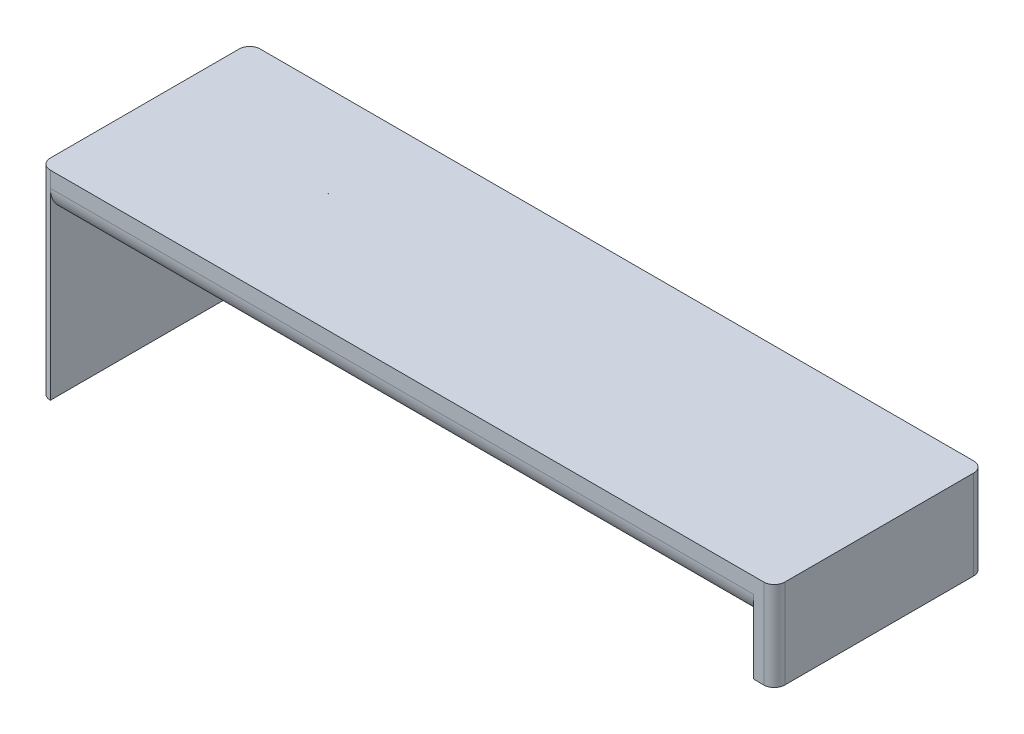
SolidWorks part; units mm, degrees
ref_plane "Front Plane" through (0, 0, 0) normal (0, 0, 1) x (1, 0, 0)
ref_plane "Top Plane" through (0, 0, 0) normal (0, 1, 0) x (1, 0, 0)
ref_plane "Right Plane" through (0, 0, 0) normal (1, 0, 0) x (0, 0, -1)
sketch "Sketch1" plane through (0, 0, 0) normal (0, 1, 0) x (1, 0, 0)
  line L1 (-70, 20) -> (70, 20)
  line L2 (-70, 20) -> (-70, -20)
  line L3 (-70, -20) -> (70, -20)
  line L4 (70, 20) -> (70, -20)
  line L5 (-70, 20) -> (70, -20) construction
  line L6 (-70, -20) -> (70, 20) construction
  line L7 (-70, 20) -> (-68, 20)
  line L8 (-70, 20) -> (-70, -20)
  line L9 (-70, -20) -> (-68, -20)
  line L10 (-68, 20) -> (-68, -20)
  line L11 (-70, 20) -> (-68, -20) construction
  line L12 (-70, -20) -> (-68, 20) construction
  line L13 (70, 20) -> (68, 20)
  line L14 (70, 20) -> (70, -20)
  line L15 (70, -20) -> (68, -20)
  line L16 (68, 20) -> (68, -20)
  line L17 (70, 20) -> (68, -20) construction
  line L18 (70, -20) -> (68, 20) construction
  point P0 (0, 0)
  point P8 (-69, 0)
  point P11 (69, 0)
  dimension "D1" = 140
  dimension "D2" = 40
  dimension "D3" = 2
  dimension "D4" = 2
extrude "Boss-Extrude1" add sketch "Sketch1" along normal blind 8 contours L16 L1 L10 L3 | L1 L16 L3 L4 | L10 L1 L2 L3 region at (-69, 0, 0) region at (0, 0, 0) region at (69, 0, 0)
extrude "Boss-Extrude2" add sketch "Sketch1<3>" against normal blind 9 contours L1 L16 L3 L4 region at (69, 0, 0)
sketch "Sketch1<3>" plane through (0, 0, 0) normal (0, 1, 0) x (1, 0, 0) same geometry as "Sketch1"
sketch "Sketch2" plane through (68, 0, 0) normal (-1, 0, 0) x (0, 0, 1)
  line L0 (-20, 0) -> (20, 0) construction
  line L1 (9.125, 0) -> (-9.125, 0)
  line L2 (9.125, 0) -> (9.125, -9)
  line L3 (9.125, -9) -> (-9.125, -9)
  line L4 (-9.125, 0) -> (-9.125, -9)
  line L5 (9.125, 0) -> (-9.125, -9) construction
  line L6 (9.125, -9) -> (-9.125, 0) construction
  line L7 (-20, -9) -> (-20, 0) construction
  line L8 (9.125, -9) -> (8.525, -9)
  line L9 (9.125, -9) -> (9.125, 0)
  line L10 (9.125, 0) -> (8.525, 0)
  line L11 (8.525, -9) -> (8.525, 0)
  line L12 (9.125, -9) -> (8.525, 0) construction
  line L13 (9.125, 0) -> (8.525, -9) construction
  line L14 (-9.125, -9) -> (-8.525, -9)
  line L15 (-9.125, -9) -> (-9.125, 0)
  line L16 (-9.125, 0) -> (-8.525, 0)
  line L17 (-8.525, -9) -> (-8.525, 0)
  line L18 (-9.125, -9) -> (-8.525, 0) construction
  line L19 (-9.125, 0) -> (-8.525, -9) construction
  line L20 (8.525, -0.6) -> (-8.525, -0.6)
  line L21 (8.525, -0.6) -> (8.525, 0)
  line L22 (8.525, 0) -> (-8.525, 0)
  line L23 (-8.525, -0.6) -> (-8.525, 0)
  line L24 (8.525, -0.6) -> (-8.525, 0) construction
  line L25 (8.525, 0) -> (-8.525, -0.6) construction
  line L26 (-9.125, -9) -> (-20, -9)
  line L27 (-9.125, -9) -> (-9.125, 0)
  line L28 (-9.125, 0) -> (-20, 0)
  line L29 (-20, -9) -> (-20, 0)
  line L30 (-9.125, -9) -> (-20, 0) construction
  line L31 (-9.125, 0) -> (-20, -9) construction
  line L33 (9.125, -9) -> (20, -9)
  line L34 (9.125, -9) -> (9.125, 0)
  line L35 (9.125, 0) -> (20, 0)
  line L36 (20, -9) -> (20, 0)
  line L37 (9.125, -9) -> (20, 0) construction
  line L38 (9.125, 0) -> (20, -9) construction
  point P4 (0, -4.5)
  point P7 (0, 0)
  point P11 (8.825, -4.5)
  point P14 (-8.825, -4.5)
  point P18 (0, -0.3)
  point P20 (-14.5625, -4.5)
  point P25 (14.5625, -4.5)
  line M3 (20, 0) -> (-20, 0)
  line M4 (-20, 0) -> (-20, -9)
  line M6 (20, -9) -> (20, 0)
  dimension "D1" = 18.25
  dimension "D2" = 9
  dimension "D3" = 0.6
  dimension "D4" = 0.6
  dimension "D5" = 0.6
extrude "Boss-Extrude3" add sketch "Sketch2" along normal blind 1 contours L2 L33 M6 M3 | L26 L4 M3 M4 region at (68, -4.5, 14.5625) region at (68, -4.5, -14.5625)
extrude "Boss-Extrude4" add sketch "Sketch2<3>" along normal blind 1 from surface contours L11 L3 L2 M3 | L2 L33 M6 M3 | L20 L11 L1 L17 | L3 L17 L4 M3 | L26 L4 M3 M4 region at (68, -4.5, 8.825) region at (68, -4.5, 14.5625) region at (68, -0.3, 0) region at (68, -4.5, -8.825) region at (68, -4.5, -14.5625) starting at face at (67, -4.5, 14.5625)
sketch "Sketch2<3>" plane through (68, 0, 0) normal (-1, 0, 0) x (0, 0, 1) same geometry as "Sketch2"
ref_plane "Plane1" through (64, 0, 0) normal (-1, 0, 0) x (0, 0, 1)
extrude "Boss-Extrude5" add sketch "Sketch1<4>" against normal blind 30 contours L10 L1 L2 L3 region at (-69, 0, 0)
sketch "Sketch1<4>" plane through (0, 0, 0) normal (0, 1, 0) x (1, 0, 0) same geometry as "Sketch1"
sketch "Sketch3" plane through (64, 0, 0) normal (-1, 0, 0) x (0, 0, 1)
  line L0 (0, 0) -> (0, -6.5) construction
  line L1 (11.6554, -3.25) -> (-11.6554, -3.25)
  line L2 (-11.6554, -3.25) -> (-11.6554, 0)
  line L3 (-11.6554, 0) -> (0, 0)
  line L4 (0, 0) -> (11.6554, 0)
  line L5 (-20, 0) -> (20, 0) construction
  line L6 (11.6554, 0) -> (11.6554, -3.25)
  circle A0 centre (0, -6.5) radius 12.1
  point P7 (0, -3.25)
  dimension "D1" = 24.2
  dimension "D2" = 6.5
extrude "Cut-Extrude1" cut sketch "Sketch3" along normal up to surface (132 mm away) contours L1 A0 | L4 L0 L1 A0 | L0 L3 A0 L1 | L4 A0 L3 region at (64, -1.6604, 5.5213) region at (64, -1.6604, -5.5213) region at (64, 2.2914, 0) region at (64, -9.9308, 0) up to face at (-68, -15, 0)
fillet "Fillet1" radius 5 2 edges at (-1, 0, 20) (-1, 0, -20)
fillet "Fillet2" radius 2 4 edges at (-70, -11, 20) (-70, -11, -20) (70, -0.5, 20) (70, -0.5, -20)
extrude "Boss-Extrude6" add sketch "Sketch3<3>" along normal up to surface and the other way up to surface contours A0 L3 L2 | A0 L6 L4 region at (64, -1.0038, 11.2018) region at (64, -1.0038, -11.2018) up to face at (-68, -5.8089, 0) other way up to face at (66, -2.9271, 0)
sketch "Sketch3<3>" plane through (64, 0, 0) normal (-1, 0, 0) x (0, 0, 1) same geometry as "Sketch3"
fillet "Fillet3" radius 0.5 2 edges at (-1, -3.25, -11.6554) (-1, -3.25, 11.6554)
fillet "Fillet5" radius 1 1 edges at (64, 0, 0)
